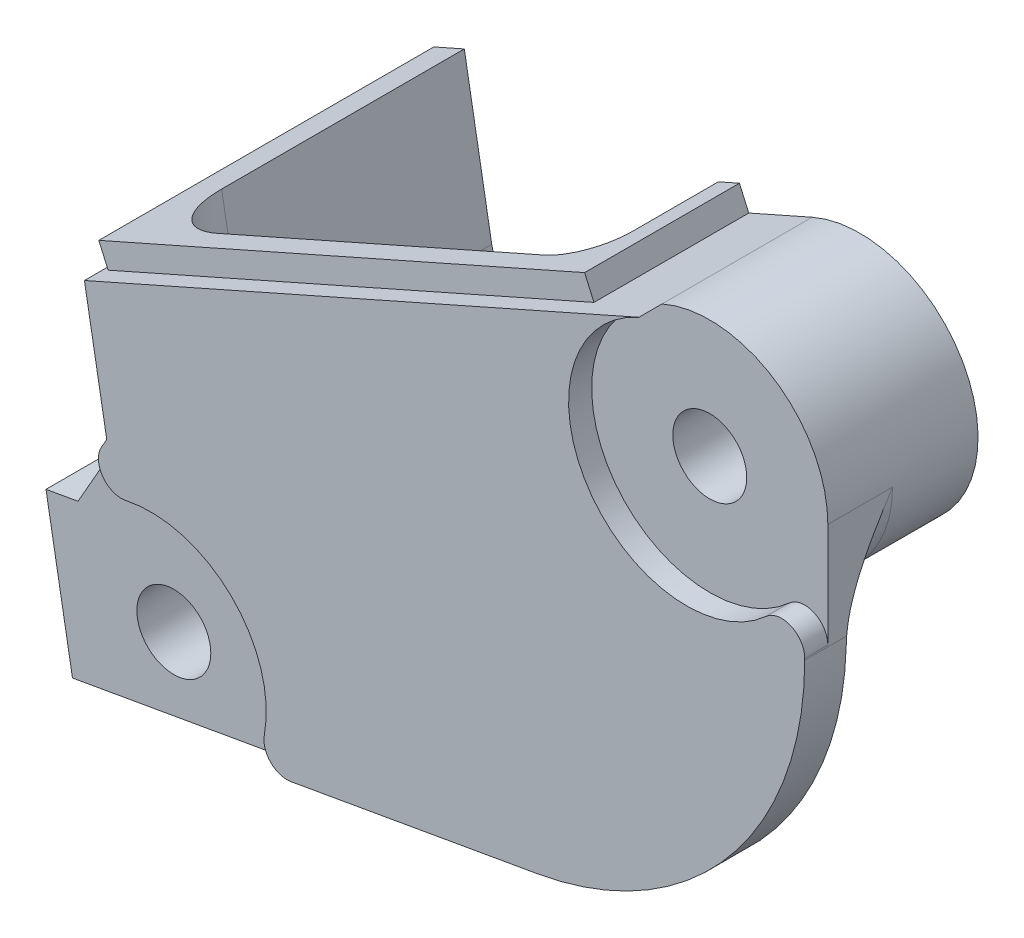
SolidWorks part; units mm, degrees
ref_plane "前视基准面" through (0, 0, 0) normal (0, 0, 1) x (1, 0, 0)
ref_plane "上视基准面" through (0, 0, 0) normal (0, 1, 0) x (1, 0, 0)
ref_plane "右视基准面" through (0, 0, 0) normal (1, 0, 0) x (0, 0, -1)
other "Configuration Table"
sketch "草图1" plane through (0, 0, 0) normal (0, 0, 1) x (1, 0, 0)
  line L0 (-7.0476, 5.9136) -> (0, 5.9136) construction
  line L1 (0, 5.9136) -> (0, 0) construction
  line L2 (0, 0) -> (-7.0476, 5.9136) construction
  line L3 (-12.4776, 6.0041) -> (2.6676, 12.706)
  line L4 (2.6676, 12.706) -> (2.6676, -8.6685)
  line L5 (-12.4776, 6.0041) -> (-12.4776, -11.339)
  line L6 (-12.4776, -11.339) -> (2.6676, -8.6685)
  circle A0 centre (0, 0) radius 1
  circle A1 centre (-7.0476, 5.9136) radius 1
  dimension "D1" = 9.2
  dimension "D3" = 2
  dimension "D4" = 2
  dimension "D9" = 5.43
  dimension "D8" = 9
  dimension "D2" = 50
  dimension "D5" = 2.28
  dimension "D6" = 63.87
  dimension "D7" = 2.6676
  dimension "D10" = 50
extrude "凸台-拉伸1" add sketch "草图1" along normal blind 1.4
sketch "草图2" plane through (0, 0, 0) normal (0, 0, -1) x (-1, 0, 0)
  circle A0 centre (7.0476, 5.9136) radius 2
  circle A1 centre (7.0476, 5.9136) radius 1 construction
  circle A2 centre (7.0476, 5.9136) radius 1
  dimension "D1" = 4
extrude "凸台-拉伸2" add sketch "草图2" along normal blind 1
sketch "草图3" plane through (0, 0, 0) normal (0, 0, -1) x (-1, 0, 0)
  circle A0 centre (0, 0) radius 2
  circle A1 centre (0, 0) radius 1 construction
  circle A2 centre (0, 0) radius 1
  circle A4 centre (7.0476, 5.9136) radius 2 construction
extrude "凸台-拉伸3" add sketch "草图3" along normal blind 0.4
sketch "草图4" plane through (0, 0, 1.4) normal (0, 0, 1) x (1, 0, 0)
  circle A0 centre (-7.0476, 5.9136) radius 1 construction
  circle A1 centre (-7.0476, 5.9136) radius 1
extrude "凸台-拉伸4" add sketch "草图4" against normal blind 1
sketch "草图5" plane through (0, 0, 1.4) normal (0, 0, 1) x (1, 0, 0)
  line L0 (0, 0) -> (8.1261, 1.4328) construction
  line L1 (8.1261, 1.4328) -> (8.1261, 9.5328) construction
  line L2 (-12.4776, -11.339) -> (2.6676, -8.6685) construction
  line L5 (2.6676, 12.706) -> (2.6676, -8.6685)
  line L6 (2.6676, -8.6685) -> (13.2367, -6.8049)
  line L7 (13.2367, -6.8049) -> (13.2367, 9.5328)
  line L8 (-12.4776, -11.339) -> (-14.5289, -11.7007) construction
  line L9 (-14.5289, -11.7007) -> (-15.0672, -8.6478) construction
  line L10 (0, 0) -> (1.5628, -8.8633) construction
  line L11 (-12.4776, -11.339) -> (-18.3923, -12.3819)
  line L12 (-12.4776, 6.0041) -> (-19.4121, -6.1736)
  line L13 (-12.4776, 6.0041) -> (-12.4776, -11.339)
  line L14 (2.6676, 12.706) -> (6.058, 14.2063)
  line L15 (2.6676, 12.706) -> (-12.4776, 6.0041) construction
  line L16 (8.1261, 9.5328) -> (9.5113, 1.6771) construction
  line L17 (9.5113, 1.6771) -> (8.1261, 1.4328) construction
  arc A0 (13.2367, 9.5328) -> (6.058, 14.2063) centre (8.1261, 9.5328) ccw
  arc A4 (-19.4121, -6.1736) -> (-18.3923, -12.3819) centre (-15.0672, -8.6478) ccw
  dimension "D1" = 8.1
  dimension "D2" = 9.658
  dimension "D3" = 16.34
  dimension "D5" = 5
  dimension "D4" = 3.1
extrude "凸台-拉伸5" add sketch "草图5" against normal up to surface (1.4 mm away) up to face at (-5.0476, 5.9136, 0)
sketch "草图6" plane through (0, 0, 1.4) normal (0, 0, 1) x (1, 0, 0)
  line L4 (6.058, 14.2063) -> (-12.4776, 6.0041)
  line L5 (-12.4776, 6.0041) -> (-19.4121, -6.1736)
  line L6 (-18.3923, -12.3819) -> (13.2367, -6.8049)
  line L7 (13.2367, -6.8049) -> (13.2367, 9.5328)
  line L8 (6.058, 14.2063) -> (-12.4776, 6.0041)
  line L9 (-12.4776, 6.0041) -> (-19.4121, -6.1736)
  line L10 (-18.3923, -12.3819) -> (13.2367, -6.8049)
  line L11 (13.2367, -6.8049) -> (13.2367, 9.5328)
  arc A2 (-19.4121, -6.1736) -> (-18.3923, -12.3819) centre (-15.0672, -8.6478) ccw
  arc A3 (13.2367, 9.5328) -> (6.058, 14.2063) centre (8.1261, 9.5328) ccw
  arc A4 (-19.4121, -6.1736) -> (-18.3923, -12.3819) centre (-15.0672, -8.6478) ccw
  arc A5 (13.2367, 9.5328) -> (6.058, 14.2063) centre (8.1261, 9.5328) ccw
  dimension "D1" = 0
extrude "凸台-拉伸6" add sketch "草图6" along normal blind 0.4
sketch "草图7" plane through (0, 0, 0) normal (0, 0, -1) x (-1, 0, 0)
  line L0 (10.6655, -11.0195) -> (18.3923, -12.3819)
  line L1 (18.3923, -12.3819) -> (-13.2367, -6.8049) construction
  circle A0 centre (15.0672, -8.6478) radius 1.6
  arc A1 (18.3923, -12.3819) -> (19.4121, -6.1736) centre (15.0672, -8.6478) ccw construction
  arc A2 (18.3923, -12.3819) -> (10.6655, -11.0195) centre (15.0672, -8.6478) ccw
  dimension "D1" = 3.2
extrude "凸台-拉伸7" add sketch "草图7" along normal blind 8.7
sketch "草图8" plane through (0, 0, 0) normal (0, 0, -1) x (-1, 0, 0)
  circle A0 centre (-8.1261, 9.5328) radius 5.1106
  circle A1 centre (-8.1261, 9.5328) radius 1.6
  circle A2 centre (15.0672, -8.6478) radius 1.6 construction
extrude "凸台-拉伸8" add sketch "草图8" along normal blind 5.7
sketch "草图9" plane through (0, 0, 0) normal (0, 0, -1) x (-1, 0, 0)
  line L0 (10.6655, -11.0195) -> (-0.2432, -9.096)
  line L1 (10.6655, -11.0195) -> (-13.2367, -6.8049) construction
  line L2 (-0.2432, -9.096) -> (-0.0695, -8.1112)
  line L3 (-0.0695, -8.1112) -> (10.2339, -9.9279)
  arc A0 (18.3923, -12.3819) -> (10.6655, -11.0195) centre (15.0672, -8.6478) ccw construction
  arc A1 (10.2339, -9.9279) -> (10.6655, -11.0195) centre (15.0672, -8.6478) ccw
  dimension "D1" = 15
  dimension "D2" = 1
extrude "凸台-拉伸9" add sketch "草图9" along normal up to surface (8.7 mm away) up to face at (-15.2322, -7.7122, -8.7)
sketch "草图10" plane through (-4.265, 9.6382, 0) normal (-0.4047, 0.9145, 0) x (0.9145, 0.4047, 0)
  line L0 (11.2886, 0) -> (11.2886, -1.8) construction
  line L1 (-8.9807, 0) -> (11.2886, 0)
  line L2 (-8.9807, 0) -> (-8.9807, -1)
  line L3 (-8.9807, -1) -> (11.2886, -1)
  line L4 (11.2886, 0) -> (11.2886, -1)
  dimension "D1" = 1
extrude "凸台-拉伸10" add sketch "草图10" along normal blind 1
sketch "草图12" plane through (0, 0, 1.8) normal (0, 0, 1) x (1, 0, 0)
  line L0 (-15.0672, -8.6478) -> (-17.2763, 3.8806) construction
  line L1 (-18.3923, -12.3819) -> (13.2367, -6.8049) construction
  line L2 (6.058, 14.2063) -> (-12.4776, 6.0041) construction
  line L3 (-12.4776, 6.0041) -> (-17.2763, 3.8806)
  line L4 (-17.2763, 3.8806) -> (-16.4276, -0.9325)
  line L5 (-12.4776, 6.0041) -> (-19.4121, -6.1736) construction
  line L6 (-12.4776, 6.0041) -> (-16.4276, -0.9325)
extrude "凸台-拉伸12" add sketch "草图12" against normal up to surface (1.8 mm away) up to face at (2, 0, 0)
sketch "草图11" plane through (0, 0, 0) normal (0, 0, -1) x (-1, 0, 0)
  line L1 (16.6163, -3.8938) -> (15.2376, -3.6507)
  line L2 (16.6163, -3.8938) -> (18.1145, 4.6032)
  line L3 (18.1145, 4.6032) -> (16.7958, 5.1867)
  line L4 (15.2376, -3.6507) -> (16.7958, 5.1867)
  line L5 (10.2339, -9.9279) -> (-0.0695, -8.1112) construction
  line L6 (17.2763, 3.8806) -> (12.4776, 6.0041) construction
  line L7 (-5.6534, 15.1208) -> (12.8823, 6.9185) construction
  arc A1 (19.4121, -6.1736) -> (10.2339, -9.9279) centre (15.0672, -8.6478) ccw construction
  dimension "D1" = 1.4
  dimension "D2" = 90
extrude "凸台-拉伸11" add sketch "草图11" along normal up to surface (8.7 mm away) up to face at (-7.627, -8.0554, -8.7)
sketch "草图13" plane through (0, 0, 0) normal (0, 0, 1) x (1, 0, 0)
  line L6 (-16.4276, -0.9325) -> (-17.2763, 3.8806)
  line L7 (-17.2763, 3.8806) -> (-16.617, 4.1723)
  line L8 (-16.617, 4.1723) -> (-16.7958, 5.1867)
  line L9 (-16.7958, 5.1867) -> (-18.1145, 4.6032)
  line L10 (-18.1145, 4.6032) -> (-16.9704, -1.8856)
  line L11 (-16.9704, -1.8856) -> (-16.4276, -0.9325)
  line L12 (-16.4276, -0.9325) -> (-17.2763, 3.8806)
  line L13 (-17.2763, 3.8806) -> (-16.617, 4.1723)
  line L14 (-16.617, 4.1723) -> (-16.7958, 5.1867)
  line L15 (-16.7958, 5.1867) -> (-18.1145, 4.6032)
  line L16 (-18.1145, 4.6032) -> (-16.9704, -1.8856)
  line L17 (-16.9704, -1.8856) -> (-16.4276, -0.9325)
  dimension "D1" = 0
extrude "凸台-拉伸13" add sketch "草图13" along normal up to surface (1.8 mm away) up to face at (-5.5441, 0.4418, 1.8)
sketch "草图14" plane through (-8.2126, -3.6342, 0) normal (-0.9145, -0.4047, 0) x (0, 0, 1)
  line L4 (0, 10.5397) -> (1, 10.5397)
  line L5 (1, 10.5397) -> (1, 11.5397)
  line L6 (1, 11.5397) -> (0, 11.5397)
  line L7 (0, 11.5397) -> (0, 10.5397)
  line L8 (0, 10.5397) -> (1, 10.5397)
  line L9 (1, 10.5397) -> (1, 11.5397)
  line L10 (1, 11.5397) -> (0, 11.5397)
  line L11 (0, 11.5397) -> (0, 10.5397)
  dimension "D1" = 0
extrude "凸台-拉伸14" add sketch "草图14" along normal up to surface (4.2796 mm away) up to face at (-16.2168, 1.9028, -2.3)
sketch "草图15" plane through (0, 0, 0) normal (0, 0, -1) x (-1, 0, 0)
  line L0 (-2.91, 13.9068) -> (-3.3146, 12.9923)
  line L1 (-5.6534, 15.1208) -> (16.7958, 5.1867) construction
  line L2 (-2.91, 13.9068) -> (-1.9955, 13.5021)
  line L3 (-1.9955, 13.5021) -> (-3.181, 10.823)
  line L4 (-3.3146, 12.9923) -> (-6.058, 14.2063)
  circle A0 centre (-8.1261, 9.5328) radius 5.1106 construction
  circle A1 centre (-8.1261, 9.5328) radius 1.6 construction
  arc A2 (-3.181, 10.823) -> (-3.7084, 12.1024) centre (-8.1261, 9.5328) ccw
  arc A3 (-13.2367, 9.5328) -> (-6.058, 14.2063) centre (-8.1261, 9.5328) ccw construction
  arc A4 (-3.181, 10.823) -> (-6.058, 14.2063) centre (-8.1261, 9.5328) ccw
  line M7 (16.7958, 5.1867) -> (-5.6534, 15.1208)
  arc M9 (-6.058, 14.2063) -> (-13.2367, 9.5328) centre (-8.1261, 9.5328) cw
  dimension "D1" = 3
  dimension "D2" = 1
extrude "凸台-拉伸15" add sketch "草图15" along normal up to surface (5.7 mm away) contours L0 L4 L3 M9 M7 region at (3.2475, 12.702, 0) up to face at (3.0155, 9.5328, -5.7)
sketch "草图16" plane through (0, 0, -8.7) normal (0, 0, -1) x (-1, 0, 0)
  line L0 (15.3649, -2.9284) -> (16.6836, -3.5119)
  line L6 (16.6163, -3.8938) -> (18.1145, 4.6032)
  line L7 (18.1145, 4.6032) -> (16.7958, 5.1867)
  line L8 (16.7958, 5.1867) -> (15.2376, -3.6507)
  line L9 (10.2339, -9.9279) -> (-0.0695, -8.1112)
  line L10 (-0.0695, -8.1112) -> (-0.2432, -9.096)
  line L11 (-0.2432, -9.096) -> (18.3923, -12.3819)
  line L12 (16.6836, -3.5119) -> (18.1145, 4.6032)
  line L13 (18.1145, 4.6032) -> (16.7958, 5.1867)
  line L14 (16.7958, 5.1867) -> (15.3649, -2.9284)
  arc A2 (18.3923, -12.3819) -> (16.6163, -3.8938) centre (15.0672, -8.6478) ccw
  arc A3 (15.2376, -3.6507) -> (10.2339, -9.9279) centre (15.0672, -8.6478) ccw
  line M11 (16.6163, -3.8938) -> (18.1145, 4.6032)
  line M12 (18.1145, 4.6032) -> (16.7958, 5.1867)
  line M13 (16.7958, 5.1867) -> (15.2376, -3.6507)
  dimension "D2" = 8
  dimension "D1" = 0
extrude "凸台-拉伸16" add sketch "草图16" along normal blind 4.8 contours L0 M13 M11 M12 region at (-16.7397, 0.8374, -8.7)
fillet "圆角1" radius 14 1 edges at (13.2367, -6.8049, 0.9)
fillet "圆角3" radius 2 2 edges at (7.4757, 4.4638, 0) (2.5883, 12.1626, 0)
sketch "草图17" plane through (0, 0, 0) normal (0, 0, -1) x (-1, 0, 0)
  circle A1 centre (15.0672, -8.6478) radius 1.6
  circle A2 centre (15.0672, -8.6478) radius 1.6
  circle A3 centre (-8.1261, 9.5328) radius 1.6
  circle A4 centre (-8.1261, 9.5328) radius 1.6
  dimension "D1" = 0
  dimension "D2" = 0
extrude "切除-拉伸1" cut sketch "草图17" against normal through all
sketch "草图18" plane through (0, 0, 1.8) normal (0, 0, 1) x (1, 0, 0)
  circle A0 centre (-15.0672, -8.6478) radius 5
  circle A1 centre (8.1261, 9.5328) radius 5.1106
extrude "切除-拉伸2" cut sketch "草图18" against normal blind 1
fillet "圆角4" radius 1 3 edges at (13.2367, 9.5328, 1.3) (-19.4121, -6.1736, 1.3) (-10.6655, -11.0195, 1.3)
sketch "草图19" plane through (0, 0, -8.7) normal (0, 0, -1) x (-1, 0, 0)
  line L0 (-0.2432, -9.096) -> (18.3923, -12.3819) construction
  line L1 (-0.0695, -8.1112) -> (-0.2432, -9.096) construction
  line L2 (10.2339, -9.9279) -> (-0.0695, -8.1112) construction
  line L3 (-0.2432, -9.096) -> (10.6655, -11.0195)
  line L4 (-0.0695, -8.1112) -> (-0.2432, -9.096)
  line L5 (10.2339, -9.9279) -> (-0.0695, -8.1112)
  arc A0 (10.2339, -9.9279) -> (10.6655, -11.0195) centre (15.0672, -8.6478) ccw
extrude "切除-拉伸3" cut sketch "草图19" against normal up to surface (8.7 mm away) up to face at (-5.0476, 5.9136, 0)
fillet "圆角2" radius 3 3 edges at (-15.2376, -3.6507, -4.35) (-16.0167, 0.768, 0) (-10.8186, -6.0117, 0)
sketch "草图20" plane through (-15.4024, -2.7159, 0) normal (0.9848, 0.1736, 0) x (0, 0, -1)
  line L4 (-1, 6.9945) -> (-1, 8.0245)
  line L5 (-1, 8.0245) -> (-1.8, 8.0245)
  line L6 (-1.8, 8.0245) -> (-1.8, 6.9945)
  line L7 (-1.8, 6.9945) -> (-1, 6.9945)
  line L8 (-1, 6.9945) -> (-1, 8.0245)
  line L9 (-1, 8.0245) -> (-1.8, 8.0245)
  line L10 (-1.8, 8.0245) -> (-1.8, 6.9945)
  line L11 (-1.8, 6.9945) -> (-1, 6.9945)
  dimension "D1" = 0
extrude "切除-拉伸4" cut sketch "草图20" along direction (0.9145, 0.4047, 0) on the side against the normal up to next (1.4 mm away)
sketch "草图21" plane through (0, 0, 1) normal (0, 0, 1) x (1, 0, 0)
  line L0 (-18.1145, 4.6032) -> (-17.7099, 3.6887)
  line L1 (6.058, 14.2063) -> (-17.9357, 3.5888) construction
  line L2 (-17.7099, 3.6887) -> (-17.9357, 3.5888)
  line L3 (-17.9357, 3.5888) -> (-18.1145, 4.6032)
  line L4 (5.6534, 15.1208) -> (6.058, 14.2063) construction
extrude "切除-拉伸5" cut sketch "草图21" against normal up to next
sketch "草图22" plane through (0, 0, 0) normal (0, 0, -1) x (-1, 0, 0)
  line L4 (-3.3146, 12.9923) -> (-2.91, 13.9068)
  line L5 (-2.91, 13.9068) -> (-5.6534, 15.1208)
  line L6 (-5.6534, 15.1208) -> (-6.058, 14.2063)
  line L7 (-6.058, 14.2063) -> (-3.3146, 12.9923)
  line L8 (-3.3146, 12.9923) -> (-2.91, 13.9068)
  line L9 (-2.91, 13.9068) -> (-5.6534, 15.1208)
  line L10 (-5.6534, 15.1208) -> (-6.058, 14.2063)
  line L11 (-6.058, 14.2063) -> (-3.3146, 12.9923)
  dimension "D1" = 0
extrude "切除-拉伸6" cut sketch "草图22" against normal up to next
sketch "草图23" plane through (0, 0, 0.8) normal (0, 0, 1) x (1, 0, 0)
  line L0 (-18.3923, -12.3819) -> (-19.453, -12.5689)
  line L1 (-19.453, -12.5689) -> (-19.9913, -9.516)
  line L2 (-18.3923, -12.3819) -> (-8.9938, -10.7247) construction
  arc A0 (-19.4121, -6.1736) -> (-18.3923, -12.3819) centre (-15.0672, -8.6478) ccw construction
  arc A1 (-19.9913, -9.516) -> (-18.3923, -12.3819) centre (-15.0672, -8.6478) ccw
  point P7 (0, 0)
extrude "凸台-拉伸17" add sketch "草图23" against normal up to surface (9.5 mm away) up to face at (-16.6672, -8.6478, -8.7)
sketch "草图24" plane through (0, 0, -8.7) normal (0, 0, -1) x (-1, 0, 0)
  line L0 (19.9913, -9.516) -> (20.599, -6.0692)
  line L1 (20.599, -6.0692) -> (19.1915, -5.821)
  line L2 (19.9913, -9.516) -> (19.453, -12.5689) construction
  arc A0 (19.9913, -9.516) -> (16.6163, -3.8938) centre (15.0672, -8.6478) ccw construction
  arc A1 (19.9913, -9.516) -> (19.1915, -5.821) centre (15.0672, -8.6478) ccw
  circle A2 centre (15.0672, -8.6478) radius 1.6 construction
  dimension "D1" = 3.5
extrude "凸台-拉伸18" add sketch "草图24" against normal up to surface (9.5 mm away) up to face at (-13.4672, -8.6478, 0.8)
